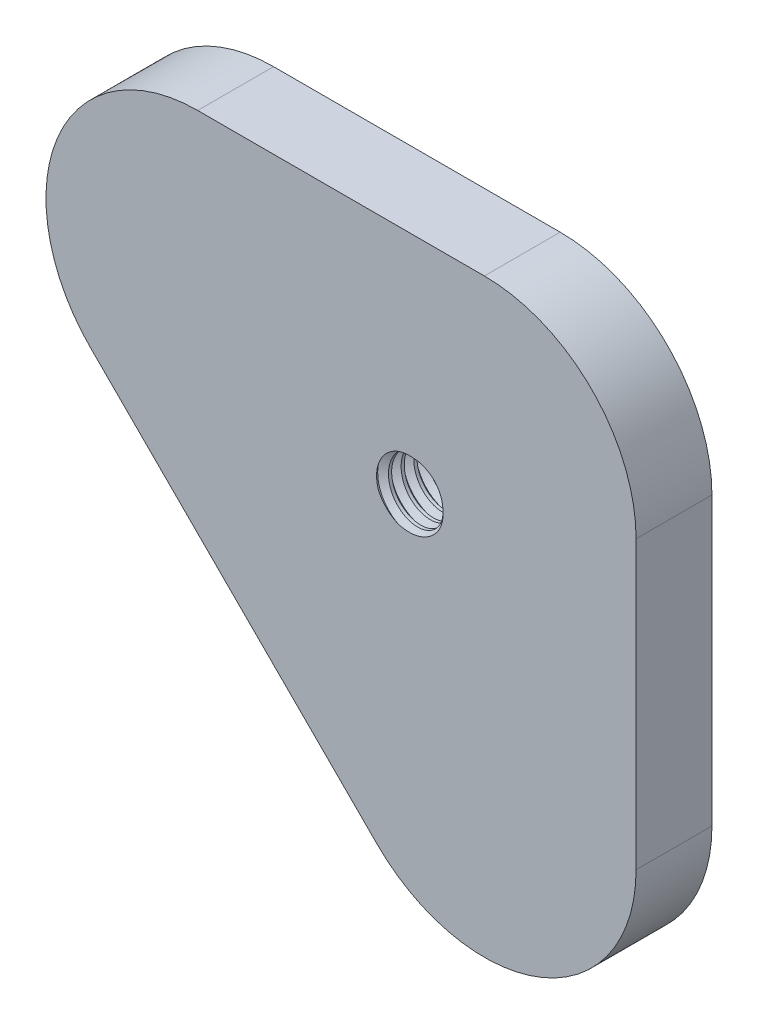
SolidWorks part; units mm, degrees
material "Plain Carbon Steel"
ref_plane "Front Plane" through (0, 0, 0) normal (0, 0, 1) x (1, 0, 0)
ref_plane "Top Plane" through (0, 0, 0) normal (0, 1, 0) x (1, 0, 0)
ref_plane "Right Plane" through (0, 0, 0) normal (1, 0, 0) x (0, 0, -1)
sketch "Sketch1" plane through (0, 0, 0) normal (0, 0, 1) x (1, 0, 0)
  line L0 (584.5147, 561.8457) -> (561.8457, 584.5147)
  line L1 (605, 600) -> (605, -600) construction
  line L2 (-600, 605) -> (600, 605) construction
  line L3 (570.331, 605) -> (593, 605)
  line L4 (605, 593) -> (605, 570.331)
  line L5 (605, 605) -> (573.1802, 573.1802) construction
  line L6 (605, 600) -> (605, 605) construction
  line L7 (605, 605) -> (600, 605) construction
  arc A0 (561.8457, 584.5147) -> (570.331, 605) centre (570.331, 593) cw
  arc A1 (584.5147, 561.8457) -> (605, 570.331) centre (593, 570.331) ccw
  arc A2 (593, 605) -> (605, 593) centre (593, 593) cw
  circle A3 centre (587.3223, 587.3223) radius 2.4
  point P10 (541.3604, 605)
  point P13 (605, 541.3604)
  point P71 (0, 0)
  dimension "D2" = 12
  dimension "D3" = 4.8
  dimension "D1" = 45
  dimension "D4" = 45
  dimension "D5" = 20
extrude "Boss-Extrude1" add sketch "Sketch1" along normal blind 6
thread "Thread1" pitch 1 method cut profile "Thread Profile1" start angle 0, offset 0, length 10, pitch 1, diameter 4.8
ref_plane "Plane1" through (589.7223, 587.3223, 0) normal (0, -1, 0) x (1, 0, 0)
sketch "Thread Profile1" plane through (589.7223, 587.3223, 0) normal (0, -1, 0) x (1, 0, 0)
  line L0 (0, 0) -> (0, 1) construction
  line L1 (0, 0) -> (0.5413, 0.3125)
  line L2 (0.5413, 0.3125) -> (0.5413, 0.4375)
  line L3 (0.5413, 0.4375) -> (0, 0.75)
  line L4 (0.5413, 0.375) -> (0, 0.375) construction
  line L11 (0, 0) -> (0, 0.75)
  point P2 (0, 0)
  dimension "Pitch" = 1
  dimension "Profile_Angle" = 60
  dimension "Profile_Land" = 0.125
  dimension "Profile_Height" = 0.5413
